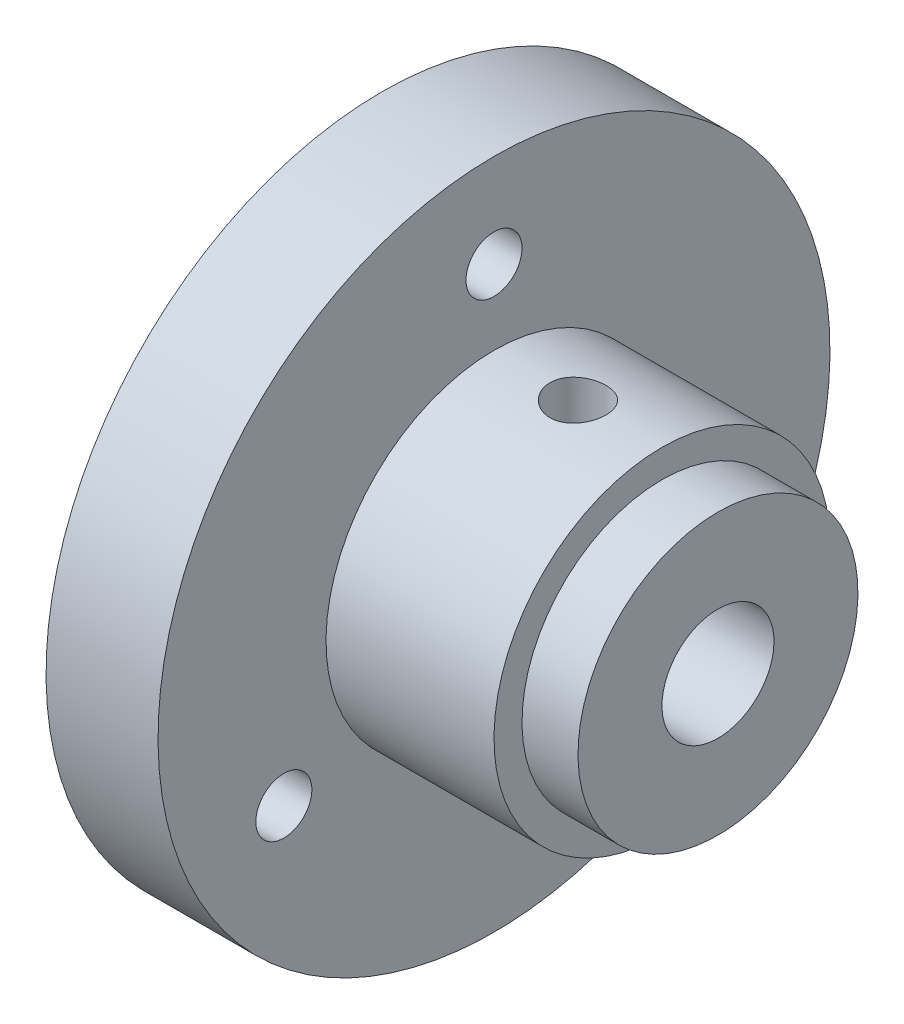
SolidWorks part; units mm, degrees
ref_plane "Plan de face" through (0, 0, 0) normal (0, 0, 1) x (1, 0, 0)
ref_plane "Plan de dessus" through (0, 0, 0) normal (0, 1, 0) x (1, 0, 0)
ref_plane "Plan de droite" through (0, 0, 0) normal (1, 0, 0) x (0, 0, -1)
sketch "Esquisse1" plane through (0, 0, 0) normal (0, 0, 1) x (1, 0, 0)
  line L0 (0, 0) -> (-18, 0) construction
  line L1 (0, 3) -> (-18, 3)
  line L3 (-3, 9) -> (-12, 9)
  line L7 (-12, 18) -> (-18, 18)
  line L8 (-18, 3) -> (-18, 18)
  line L9 (-18, 3) -> (-18, 0) construction
  line L10 (-3, 9) -> (-3, 7.5)
  line L11 (-12, 18) -> (-12, 9)
  line L14 (-3, 7.5) -> (0, 7.5)
  line L15 (0, 3) -> (0, 7.5)
  line L16 (0, 3) -> (0, 0) construction
  dimension "D1" = 3
  dimension "D2" = 18
  dimension "D3" = 6
  dimension "D4" = 6
  dimension "D5" = 9
  dimension "D6" = 7.5
  dimension "D7" = 3
revolve "Révolution1" add sketch "Esquisse1" angle 360 about L0
sketch "Esquisse2" plane through (-12, 0, 0) normal (1, 0, 0) x (0, 0, -1)
  line L0 (0, 13) -> (0, 0) construction
  circle A0 centre (0, 13) radius 1.5
  circle A1 centre (11.2583, -6.5) radius 1.5
  circle A2 centre (-11.2583, -6.5) radius 1.5
  point P11 (0, 0)
  dimension "D1" = 3
  dimension "D2" = 13
  dimension "D3" = 3
extrude "Enlèv. mat.-Extru.1" cut sketch "Esquisse2" against normal through all
ref_plane "Plan2" through (0, 9, 0) normal (0, 1, 0) x (1, 0, 0)
sketch "Esquisse3" plane through (0, 9, 0) normal (0, 1, 0) x (1, 0, 0)
  line L0 (-3, 0) -> (-12, 0) construction
  line L1 (-12, -1.5) -> (-12, 1.5) construction
  line L2 (-3, -7.5) -> (-3, 7.5) construction
  circle A0 centre (-7.5, 0) radius 1.5
  point P8 (-7.5, 0)
  dimension "D1" = 3
extrude "Enlèv. mat.-Extru.2" cut sketch "Esquisse3" against normal up to next
